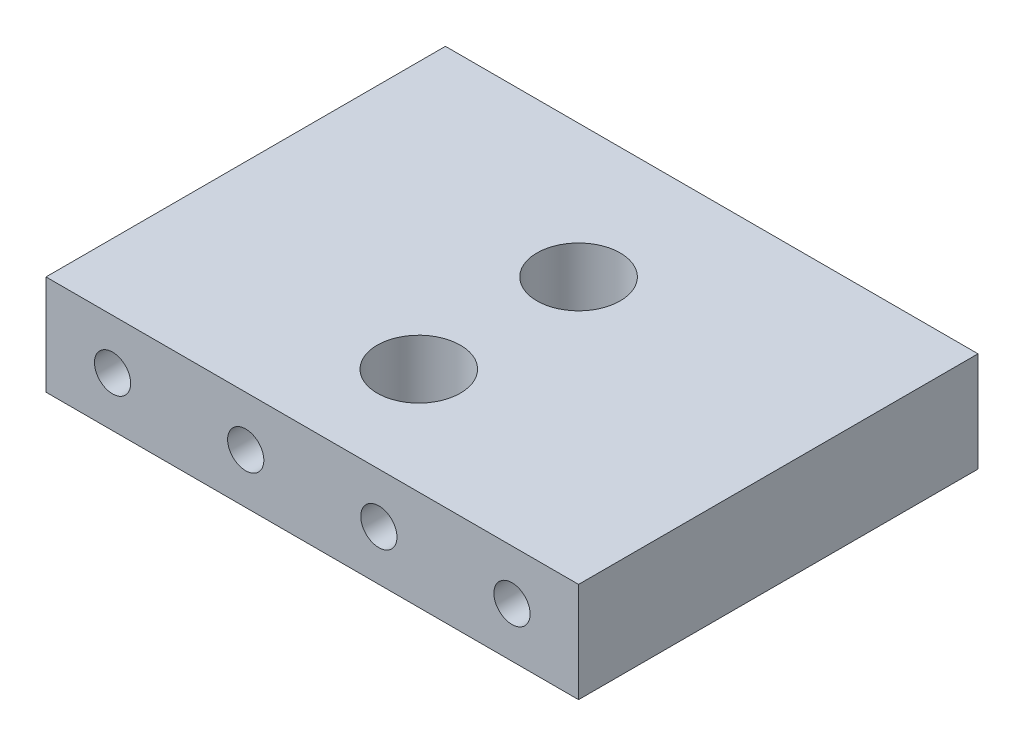
SolidWorks part; units mm, degrees
ref_plane "Front Plane" through (0, 0, 0) normal (0, 0, 1) x (1, 0, 0)
ref_plane "Top Plane" through (0, 0, 0) normal (0, 1, 0) x (1, 0, 0)
ref_plane "Right Plane" through (0, 0, 0) normal (1, 0, 0) x (0, 0, -1)
sketch "Sketch1" plane through (0, 0, 0) normal (0, 0, 1) x (1, 0, 0)
  line L0 (-25.4, -50.8) -> (-25.4, 50.8) construction
  line L1 (25.4, -4.7625) -> (-25.4, -4.7625)
  line L2 (25.4, -4.7625) -> (25.4, 4.7625)
  line L3 (25.4, 4.7625) -> (-25.4, 4.7625)
  line L4 (-25.4, -4.7625) -> (-25.4, 4.7625)
  line L5 (25.4, -4.7625) -> (-25.4, 4.7625) construction
  line L6 (25.4, 4.7625) -> (-25.4, -4.7625) construction
  circle A0 centre (-19.05, 0) radius 2.2479 construction
  circle A1 centre (-6.35, 0) radius 2.2479 construction
  circle A2 centre (6.35, 0) radius 2.2479 construction
  circle A3 centre (19.05, 0) radius 2.2479 construction
  circle A4 centre (-19.05, 0) radius 2.2479
  circle A5 centre (-6.35, 0) radius 2.2479
  circle A6 centre (6.35, 0) radius 2.2479
  circle A7 centre (19.05, 0) radius 2.2479
  point P0 (0, 0)
  dimension "D1" = 9.525
extrude "Boss-Extrude1" add sketch "Sketch1" along normal blind 38.1 contours L1 L4 L3 L2
hole_wizard "5/16 (0.3125) Diameter Hole1" positions "Sketch4" profile "Sketch5" hole size "5/16" standard "ANSI Inch" end condition through all
sketch "Sketch4" plane through (0, -4.7625, 0) normal (0, -1, 0) x (-1, 0, 0)
  line L0 (-25.4, -38.1) -> (25.4, -38.1) construction
  point P0 (0, -12.7)
  point P2 (0, -27.94)
  point P7 (0, -38.1)
  dimension "D1" = 15.24
  dimension "D2" = 10.16
sketch "Sketch5" plane through (0, -4.7625, 12.7) normal (1, 0, 0) x (0, 0, -1)
  line L0 (0, 0) -> (0, 9.525)
  line L1 (0, 9.525) -> (3.9687, 9.525)
  line L2 (3.9687, 9.525) -> (3.9688, 0)
  line L5 (3.9688, 0) -> (0, 0)
  line L11 (0, -6.35) -> (0, 107.95) construction
  dimension "Thru Hole Dia." = 7.9375
  dimension "Thru Hole Depth" = 9.525
hole_wizard "#8-36 Tapped Hole1" positions "Sketch8" profile "Sketch7" tap size "#8-36" standard "ANSI Inch" end condition through all
sketch "Sketch8" plane through (0, 0, 0) normal (0, 0, -1) x (-1, 0, 0)
  point P0 (-19.05, 0)
  point P2 (-6.35, 0)
  point P4 (6.35, 0)
  point P6 (19.05, 0)
sketch "Sketch7" plane through (19.05, 0, 0) normal (1, 0, 0) x (0, 1, 0)
  line L0 (0, 0) -> (0, 38.1)
  line L1 (0, 38.1) -> (1.7272, 38.1)
  line L2 (1.7272, 38.1) -> (1.7272, 0)
  line L5 (1.7272, 0) -> (0, 0)
  line L11 (0, -6.35) -> (0, 107.95) construction
  dimension "Thru Tap Drill Dia." = 3.4544
  dimension "Thru Tap Drill Depth" = 38.1
cosmetic thread "Hole Thread1" parameters "D2"=4.1656
cosmetic thread "Hole Thread2" parameters "D2"=4.1656
cosmetic thread "Hole Thread3" parameters "D2"=4.1656
cosmetic thread "Hole Thread4" parameters "D2"=4.1656
equation "\"TabDepth\"= 1.5"
equation "\"D1@Boss-Extrude1\"=\"TabDepth\""
